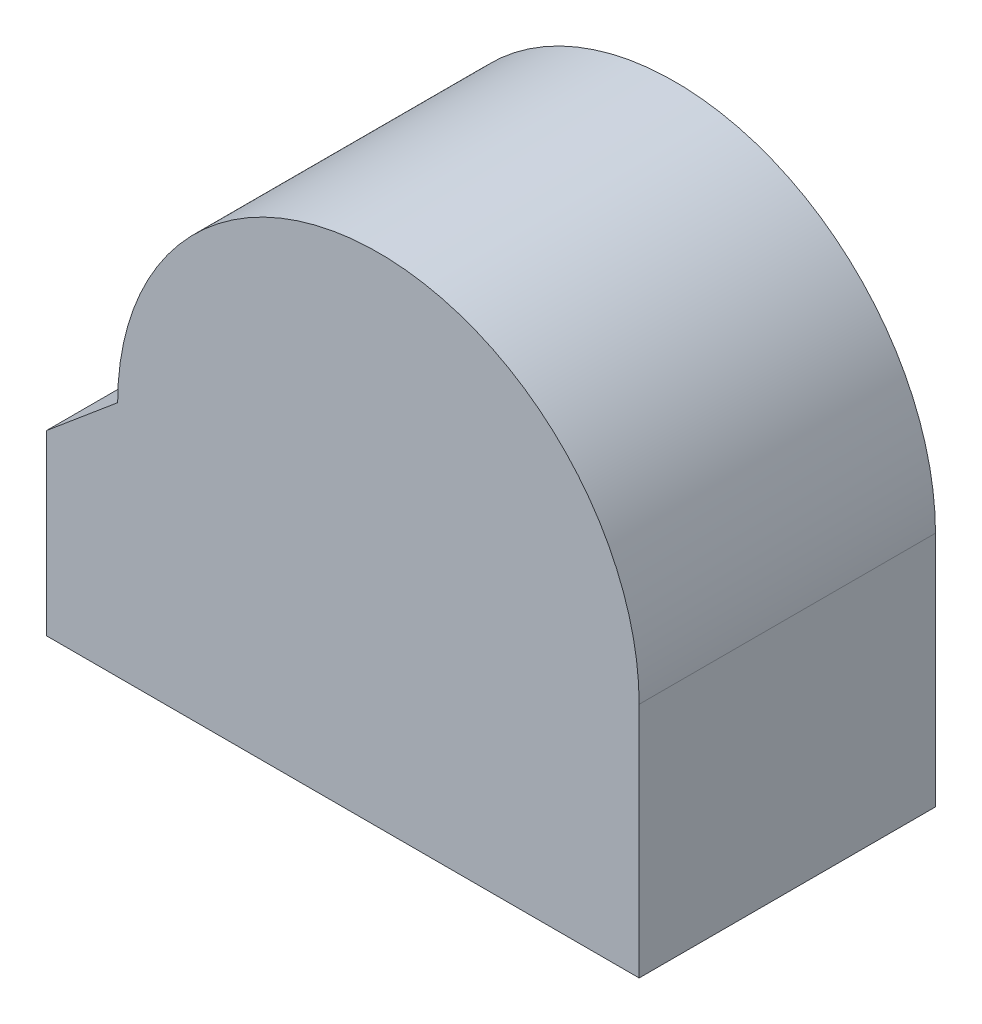
SolidWorks part; units mm, degrees
ref_plane "Alzado" through (0, 0, 0) normal (0, 0, 1) x (1, 0, 0)
ref_plane "Planta" through (0, 0, 0) normal (0, 1, 0) x (1, 0, 0)
ref_plane "Vista lateral" through (0, 0, 0) normal (1, 0, 0) x (0, 0, -1)
sketch "Croquis1" plane through (0, 0, 0) normal (0, 1, 0) x (1, 0, 0)
  line L1 (-25, -12.5) -> (25, -12.5)
  line L2 (-25, -12.5) -> (-25, 12.5)
  line L3 (-25, 12.5) -> (25, 12.5)
  line L4 (25, -12.5) -> (25, 12.5)
  line L5 (-25, -12.5) -> (25, 12.5) construction
  line L6 (-25, 12.5) -> (25, -12.5) construction
  point P0 (0, 0)
  dimension "D1" = 50
  dimension "D2" = 25
extrude "Saliente-Extruir1" add sketch "Croquis1" along normal blind 20
sketch "Croquis2" plane through (0, 0, 12.5) normal (0, 0, 1) x (1, 0, 0)
  line L0 (-19, 20) -> (25, 20)
  line L1 (-25, 20) -> (25, 20) construction
  arc A0 (25, 20) -> (-19, 20) centre (3, 20) ccw
  arc A1 (23, 20) -> (-17, 20) centre (3, 20) ccw
  line M5 (25, 20) -> (-25, 20)
  dimension "D1" = 22
  dimension "D2" = 20
extrude "Saliente-Extruir2" add sketch "Croquis2" against normal up to surface (25 mm away) contours A1 A0 M5 region at (3, 41.5081, 12.5) up to face at (0, 10, -12.5)
extrude "Saliente-Extruir3" add sketch "Croquis2<6>" against normal blind 2 contours L0 A1 region at (3, 28.4883, 12.5)
sketch "Croquis2<6>" plane through (0, 0, 12.5) normal (0, 0, 1) x (1, 0, 0) same geometry as "Croquis2"
sketch "Croquis3" plane through (0, 20, 0) normal (0, 1, 0) x (1, 0, 0)
  line L4 (-17, -10.5) -> (23, -10.5)
  line L5 (23, -10.5) -> (23, 12.5)
  line L6 (23, 12.5) -> (-17, 12.5)
  line L7 (-17, 12.5) -> (-17, -10.5)
  line L8 (-17, -10.5) -> (23, -10.5)
  line L9 (23, -10.5) -> (23, 12.5)
  line L10 (23, 12.5) -> (-17, 12.5)
  line L11 (-17, 12.5) -> (-17, -10.5)
  dimension "D1" = 0
extrude "Cortar-Extruir1" cut sketch "Croquis3" against normal up to surface (20 mm away) up to face at (0, 0, 0)
chamfer "Chaflán1" distance 5 angle 50 1 edges at (-25, 20, 0) first distance on face at (-25, 10, 0)
equation "\"2.5.00mm\"=5"
